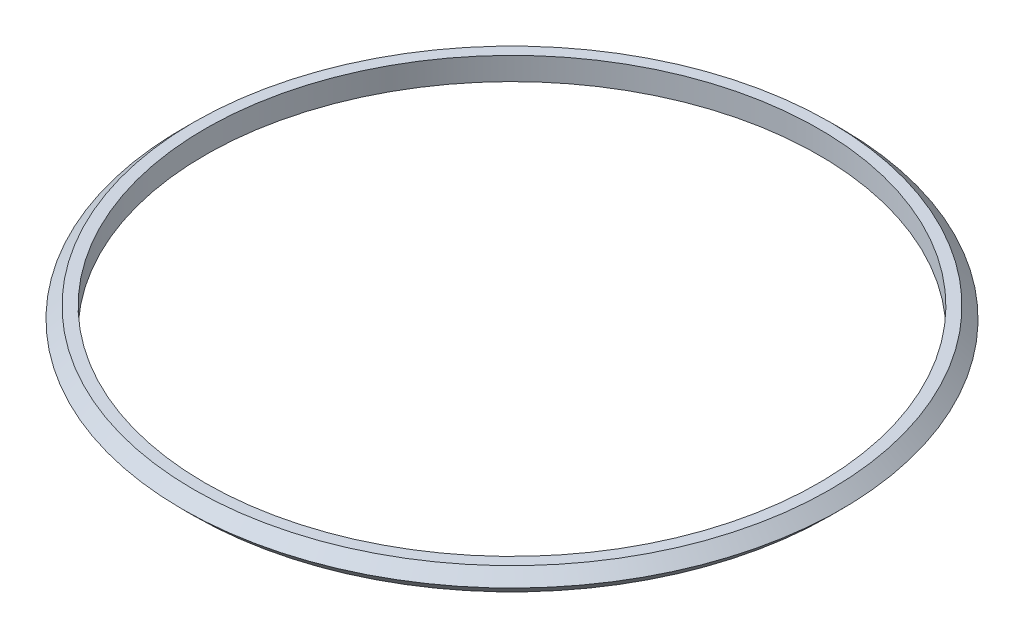
SolidWorks part; units mm, degrees
ref_plane "Plan de face" through (0, 0, 0) normal (0, 0, 1) x (1, 0, 0)
ref_plane "Plan de dessus" through (0, 0, 0) normal (0, 1, 0) x (1, 0, 0)
ref_plane "Plan de droite" through (0, 0, 0) normal (1, 0, 0) x (0, 0, -1)
sketch "Sketch3" plane through (0, 0, 0) normal (0, 1, 0) x (1, 0, 0)
  circle A0 centre (0, 0) radius 13.5
  circle A1 centre (0, 0) radius 14.5
  dimension "D1" = 27
  dimension "D2" = 29
extrude "Boss-Extrude2" add sketch "Sketch3" along normal blind 1
chamfer "Chamfer1" distance 0.5 angle 45 2 edges at (0, 0, 14.5) (0, 1, 14.5)
